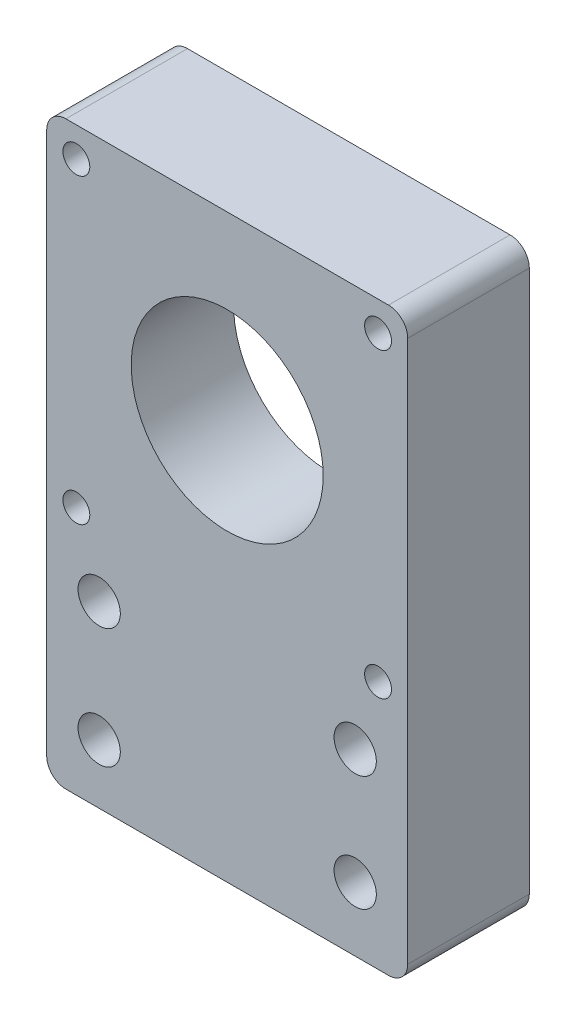
SolidWorks part; units mm, degrees
ref_plane "Front Plane" through (0, 0, 0) normal (0, 0, 1) x (1, 0, 0)
ref_plane "Top Plane" through (0, 0, 0) normal (0, 1, 0) x (1, 0, 0)
ref_plane "Right Plane" through (0, 0, 0) normal (1, 0, 0) x (0, 0, -1)
sketch "Sketch1" plane through (0, 0, 0) normal (0, 0, 1) x (1, 0, 0)
  line L4 (28.2, -3.2) -> (-28.2, -3.2)
  line L5 (28.2, 53.2) -> (28.2, -3.2)
  line L7 (-28.2, -3.2) -> (-28.2, 53.2)
  line L9 (-28.2, 53.2) -> (28.2, 53.2)
extrude "Boss-Extrude1" add sketch "Sketch1" along normal blind 19
sketch "Sketch2" plane through (0, 0, 19) normal (0, 0, 1) x (1, 0, 0)
  circle A3 centre (0, 25) radius 20.9044
extrude "Cut-Extrude2" cut sketch "Sketch2" against normal blind 20
sketch "Sketch3" plane through (0, 0, 0) normal (0, 0, -1) x (-1, 0, 0)
  line L0 (28.2, -3.2) -> (-28.2, -3.2) construction
  line L1 (-28.2, -3.2) -> (28.2, -3.2)
  line L2 (-28.2, -3.2) -> (-28.2, -37.5)
  line L3 (-28.2, -37.5) -> (28.2, -37.5)
  line L4 (28.2, -3.2) -> (28.2, -37.5)
  line L5 (-28.2, -3.2) -> (-28.2, 53.2) construction
  line L7 (-126, -17.5) -> (126, -17.5) construction
  dimension "D1" = 20
extrude "Boss-Extrude2" add sketch "Sketch3" against normal blind 19
fillet "Fillet1" radius 3 4 edges at (28.2, -37.5, 9.5) (-28.2, -37.5, 9.5) (28.2, 53.2, 9.5) (-28.2, 53.2, 9.5)
hole_wizard "Tap Drill for M5 Tap1" positions "Sketch4" profile "Sketch5" hole size "M5" standard "ISO" end condition through all
sketch "Sketch4" plane through (0, 0, 0) normal (0, 0, -1) x (-1, 0, 0)
  point P0 (-23.57, 48.57)
  point P2 (23.57, 48.57)
  point P4 (-23.57, 1.43)
  point P6 (23.57, 1.43)
sketch "Sketch5" plane through (23.57, 48.57, 0) normal (1, 0, 0) x (0, 1, 0)
  line L0 (0, 0) -> (0, 19)
  line L1 (0, 19) -> (2.1, 19)
  line L2 (2.1, 19) -> (2.1, 0)
  line L5 (2.1, 0) -> (0, 0)
  line L11 (0, -6.35) -> (0, 107.95) construction
  dimension "Thru Hole Dia." = 4.2
  dimension "Thru Hole Depth" = 19
hole_wizard "M6 Clearance Hole1" positions "Sketch6" profile "Sketch7" hole size "M6" standard "ISO" end condition through all
sketch "Sketch6" plane through (0, 0, 0) normal (0, 0, -1) x (-1, 0, 0)
  point P0 (-20, -9.5)
  point P2 (-20, -27.5)
  point P4 (20, -28.2377)
  point P6 (20, -9.5)
sketch "Sketch7" plane through (20, -9.5, 0) normal (1, 0, 0) x (0, 1, 0)
  line L0 (0, 0) -> (0, 19)
  line L1 (0, 19) -> (3.3, 19)
  line L2 (3.3, 19) -> (3.3, 0)
  line L5 (3.3, 0) -> (0, 0)
  line L11 (0, -6.35) -> (0, 107.95) construction
  dimension "Thru Hole Dia." = 6.6
  dimension "Thru Hole Depth" = 19
sketch "Sketch8" plane through (0, 0, 19) normal (0, 0, 1) x (1, 0, 0)
  circle A0 centre (0, 25) radius 20.9044 construction
  circle A1 centre (0, 25) radius 20.9044
  circle A5 centre (0, 25) radius 15
extrude "Boss-Extrude3" add sketch "Sketch8" against normal blind 16
